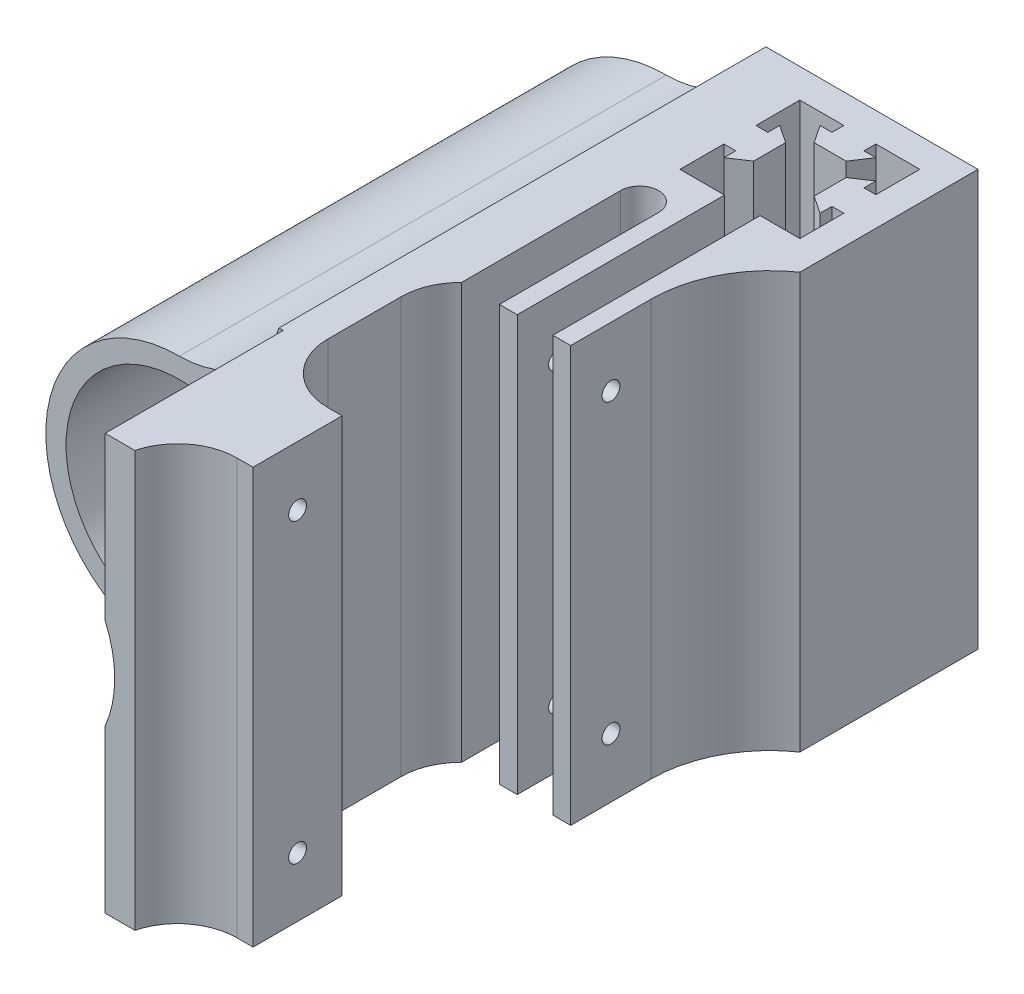
SolidWorks part; units mm, degrees
ref_plane "Front Plane" through (0, 0, 0) normal (0, 0, 1) x (1, 0, 0)
ref_plane "Top Plane" through (0, 0, 0) normal (0, 1, 0) x (1, 0, 0)
ref_plane "Right Plane" through (0, 0, 0) normal (1, 0, 0) x (0, 0, -1)
sketch "Sketch4" plane through (0, 0, 0) normal (0, 0, 1) x (1, 0, 0)
  line L0 (22.5, 0) -> (22.5, -60)
  line L21 (22.5, 0) -> (22.5, 60)
  line L22 (22.5, 60) -> (17.5, 60)
  line L23 (17.5, 60) -> (17.5, 40)
  line L24 (17.5, -60) -> (22.5, -60)
  line L25 (17.5, -40) -> (17.5, -60)
  circle A0 centre (0, 0) radius 19.1
  arc A1 (0, 22.5) -> (0, -22.5) centre (0, 0) ccw
  arc A2 (0, 22.5) -> (17.5, 40) centre (0, 40) ccw
  arc A3 (17.5, -40) -> (0, -22.5) centre (0, -40) ccw
  dimension "D1" = 38.2
  dimension "D2" = 45
  dimension "D3" = 60
  dimension "D8" = 17.5
  dimension "D9" = 17.5
  dimension "D6" = 40
  dimension "D7" = 40
  dimension "D4" = 60
  dimension "D5" = 5
extrude "Boss-Extrude4" add sketch "Sketch4" along normal blind 80
sketch "Sketch5" plane through (0, 0, 0) normal (0, 0, -1) x (-1, 0, 0)
  line L0 (-17.5, 60) -> (-22.5, 60)
  line L1 (-22.5, 60) -> (-22.5, -60)
  line L2 (-22.5, -60) -> (-17.5, -60)
  line L3 (-17.5, -60) -> (-17.5, -40)
  line L4 (-17.5, 60) -> (-17.5, 40)
  arc A0 (0, -22.5) -> (0, 22.5) centre (0, 0) ccw
  arc A1 (-17.5, 40) -> (0, 22.5) centre (0, 40) ccw
  arc A2 (0, -22.5) -> (-17.5, -40) centre (0, -40) ccw
  circle A3 centre (0, 0) radius 5
  dimension "D1" = 10
  dimension "D2" = 22.5
extrude "Boss-Extrude5" add sketch "Sketch5" along normal blind 2 contours A0 A1 L4 L0 L1 L2 L3 A2
sketch "Sketch6" plane through (0, 0, -2) normal (0, 0, -1) x (-1, 0, 0)
  circle A0 centre (0, 0) radius 5
  dimension "D1" = 10
extrude "Cut-Extrude1" cut sketch "Sketch6" against normal blind 2
sketch "Sketch7" plane through (0, 0, 80) normal (0, 0, 1) x (1, 0, 0)
  line L0 (17.5, 60) -> (17.5, 7.6525)
  line L1 (17.5, -60) -> (17.5, -7.6525)
  line L2 (17.5, -60) -> (22.5, -60)
  line L3 (22.5, -60) -> (22.5, 60)
  line L4 (22.5, 60) -> (17.5, 60)
  circle A0 centre (0, 0) radius 19.1 construction
  circle A1 centre (0, 0) radius 19.1 construction
  arc A2 (17.5, -7.6525) -> (17.5, 7.6525) centre (0, 0) ccw
extrude "Boss-Extrude7" add sketch "Sketch7" along normal blind 30 contours A2 L0 L4 L3 L2 L1
sketch "Sketch8" plane through (0, 0, -2) normal (0, 0, -1) x (-1, 0, 0)
  circle A0 centre (0, 0) radius 11
  dimension "D1" = 22
extrude "Cut-Extrude2" cut sketch "Sketch8" against normal blind 30
sketch "Sketch9" plane through (0, 0, -2) normal (0, 0, -1) x (-1, 0, 0)
  line L0 (0, 0) -> (13.5, 0)
  line L1 (0, 0) -> (-13.5, 0)
  line L2 (0, 0) -> (0, 13.5)
  line L3 (0, 0) -> (0, -13.5)
  circle A0 centre (0, 13.5) radius 1.5
  circle A1 centre (13.5, 0) radius 1.5
  circle A2 centre (0, -13.5) radius 1.5
  circle A3 centre (-13.5, 0) radius 1.5
  dimension "D5" = 3
  dimension "D6" = 3
  dimension "D7" = 3
  dimension "D8" = 3
  dimension "D1" = 13.5
  dimension "D2" = 13.5
  dimension "D3" = 13.5
  dimension "D4" = 13.5
extrude "Cut-Extrude3" cut sketch "Sketch9" against normal blind 30 contours A0 | A1 | A2 | A3
sketch "Sketch11" plane through (0, -60, 0) normal (0, -1, 0) x (1, 0, 0)
  line L1 (17.5, 110) -> (22.5, 110)
  line L2 (17.5, 110) -> (17.5, -2)
  line L3 (17.5, -2) -> (22.5, -2)
  line L4 (22.5, 110) -> (22.5, -2)
extrude "Boss-Extrude8" add sketch "Sketch11" along normal blind 20
sketch "Sketch12" plane through (0, 60, 0) normal (0, 1, 0) x (1, 0, 0)
  line L1 (17.5, 2) -> (22.5, 2)
  line L2 (17.5, 2) -> (17.5, -110)
  line L3 (17.5, -110) -> (22.5, -110)
  line L4 (22.5, 2) -> (22.5, -110)
extrude "Boss-Extrude9" add sketch "Sketch12" along normal blind 20
sketch "Sketch13" plane through (17.5, 0, 0) normal (-1, 0, 0) x (0, 0, 1)
  line L0 (-2, 60) -> (26, 60)
  line L1 (-2, 80) -> (-2, 40) construction
  line L2 (26, 60) -> (54, 60)
  line L3 (54, 60) -> (82, 60)
  line L4 (82, 60) -> (110, 60)
  line L5 (110, 80) -> (110, 7.6525) construction
  line L6 (-2, -60) -> (26, -60)
  line L7 (-2, -80) -> (-2, -40) construction
  line L8 (26, -60) -> (54, -60)
  line L9 (54, -60) -> (82, -60)
  line L10 (82, -60) -> (110, -60)
  line L11 (110, -80) -> (110, -7.6525) construction
  circle A0 centre (26, 60) radius 1.5
  circle A1 centre (54, 60) radius 1.5
  circle A2 centre (82, 60) radius 1.5
  circle A3 centre (82, -60) radius 1.5
  circle A4 centre (54, -60) radius 1.5
  circle A5 centre (26, -60) radius 1.5
  dimension "D7" = 3
  dimension "D8" = 3
  dimension "D9" = 3
  dimension "D10" = 3
  dimension "D11" = 3
  dimension "D12" = 3
  dimension "D1" = 28
  dimension "D2" = 28
  dimension "D3" = 28
  dimension "D4" = 28
  dimension "D5" = 28
  dimension "D6" = 28
extrude "Cut-Extrude4" cut sketch "Sketch13" against normal blind 20 contours A0 | A1 | A2 | A3 | A4 | A5
sketch "Sketch14" plane through (17.5, 0, 0) normal (-1, 0, 0) x (0, 0, 1)
  line L0 (95, 7.6525) -> (95, 37.6525)
  line L1 (110, 7.6525) -> (80, 7.6525) construction
  line L2 (95, -7.6525) -> (95, -37.6525)
  line L3 (110, -7.6525) -> (80, -7.6525) construction
  circle A0 centre (95, 37.6525) radius 1.5
  circle A1 centre (95, -37.6525) radius 1.5
  dimension "D3" = 3
  dimension "D4" = 3
  dimension "D1" = 30
  dimension "D2" = 30
extrude "Cut-Extrude5" cut sketch "Sketch14" against normal blind 20 contours A0 | A1
sketch "Sketch16" plane through (22.5, 0, 0) normal (1, 0, 0) x (0, 0, -1)
  line L0 (2, 80) -> (2, -80) construction
  line L1 (2, 35) -> (-28, 35)
  line L2 (2, 35) -> (2, -35)
  line L3 (2, -35) -> (-28, -35)
  line L4 (-28, 35) -> (-28, -35)
  dimension "D1" = 30
  dimension "D2" = 70
  dimension "D3" = 35
extrude "Boss-Extrude10" add sketch "Sketch16" along normal blind 30
sketch "Sketch21" plane through (0, 35, 0) normal (0, 1, 0) x (1, 0, 0)
  line L0 (27.4, -2.9) -> (47.6, -2.9)
  line L1 (27.4, -2.9) -> (27.4, -23.1)
  line L2 (27.4, -23.1) -> (47.6, -23.1)
  line L3 (47.6, -2.9) -> (47.6, -23.1)
  line L4 (34.8, -2.9) -> (34.8, -4.9)
  line L5 (34.8, -4.9) -> (32.8, -4.9)
  line L6 (32.8, -4.9) -> (34.8, -7.9)
  line L7 (34.8, -7.9) -> (40.2, -7.9)
  line L8 (37.5, -2.9) -> (37.5, -23.1) construction
  line L9 (27.4, -13) -> (47.6, -13) construction
  line L10 (40.2, -2.9) -> (40.2, -4.9)
  line L11 (40.2, -4.9) -> (42.2, -4.9)
  line L12 (42.2, -4.9) -> (40.2, -7.9)
  line L13 (29.4, -15.7) -> (29.4, -17.7)
  line L14 (27.4, -15.7) -> (29.4, -15.7)
  line L15 (29.4, -17.7) -> (32.4, -15.7)
  line L16 (32.4, -10.3) -> (32.4, -15.7)
  line L17 (29.4, -8.3) -> (32.4, -10.3)
  line L18 (29.4, -10.3) -> (29.4, -8.3)
  line L19 (27.4, -10.3) -> (29.4, -10.3)
  line L20 (47.6, -10.3) -> (45.6, -10.3)
  line L21 (45.6, -10.3) -> (45.6, -8.3)
  line L22 (45.6, -8.3) -> (42.6, -10.3)
  line L23 (42.6, -10.3) -> (42.6, -15.7)
  line L24 (45.6, -17.7) -> (42.6, -15.7)
  line L25 (45.6, -15.7) -> (45.6, -17.7)
  line L26 (47.6, -15.7) -> (45.6, -15.7)
  line L29 (52.5, 2) -> (52.5, -28) construction
  line L30 (34.9, -23.1) -> (40.9, -23.1)
  line L31 (34.9, -23.1) -> (34.9, -28)
  line L32 (34.9, -28) -> (40.9, -28)
  line L33 (40.9, -23.1) -> (40.9, -28)
  line L35 (52.5, 2) -> (22.5, 2) construction
  point P18 (37.5, -7.9)
  point P31 (42.6, -13)
  line M11 (22.5, -28) -> (52.5, -28)
  dimension "D1" = 3
  dimension "D2" = 2
  dimension "D3" = 3
  dimension "D4" = 15
  dimension "D5" = 2
  dimension "D6" = 2
  dimension "D7" = 7.4
  dimension "D8" = 2
  dimension "D9" = 7.4
  dimension "D10" = 2
  dimension "D11" = 2
  dimension "D12" = 20.2
  dimension "D13" = 20.2
  dimension "D14" = 15
  dimension "D16" = 6
  dimension "D17" = 7.5
  dimension "D18" = 15
extrude "Cut-Extrude6" cut sketch "Sketch21" against normal blind 70 contours L3 L26 L25 L24 L23 L22 L21 L20 L0 L10 L11 L12 L7 L6 L5 L4 L1 L19 L18 L17 L16 L15 L13 L14 L2 | L33 L2 L31 M11 region at (37.5, 35, 13.8018) region at (37.9, 35, 25.55)
sketch "Sketch23" plane through (0, 0, 28) normal (0, 0, 1) x (1, 0, 0)
  line L0 (52.5, -35) -> (40.9, -35) construction
  line L5 (40.9, 35) -> (43.9, 35)
  line L6 (40.9, 35) -> (40.9, -35)
  line L7 (40.9, -35) -> (43.9, -35)
  line L8 (43.9, 35) -> (43.9, -35)
  line L9 (34.9, -35) -> (22.5, -35) construction
  line L10 (22.5, 35) -> (25.5, 35)
  line L11 (22.5, 35) -> (22.5, -35)
  line L12 (22.5, -35) -> (25.5, -35)
  line L13 (25.5, 35) -> (25.5, -35)
  line L15 (34.9, 35) -> (31.9, 35)
  line L16 (34.9, 35) -> (34.9, -35)
  line L17 (34.9, -35) -> (31.9, -35)
  line L18 (31.9, 35) -> (31.9, -35)
  dimension "D1" = 3
  dimension "D2" = 3
  dimension "D3" = 3
extrude "Boss-Extrude11" add sketch "Sketch23" along normal blind 30
fillet "Fillet5" 2 edges at (25.5, 0, 28) (31.9, 0, 28) type full round first side face at (25.5, 0, 43) second side face at (31.9, 0, 43) middle face at (28.7, 0, 28)
fillet "Fillet6" radius 20 1 edges at (43.9, 0, 28)
sketch "Sketch26" plane through (17.5, 0, 0) normal (-1, 0, 0) x (0, 0, 1)
  line L1 (-2, -40) -> (110, -40)
  line L2 (-2, -40) -> (-2, -80)
  line L3 (-2, -80) -> (110, -80)
  line L4 (110, -40) -> (110, -80)
  line L5 (-2, 40) -> (110, 40)
  line L6 (-2, 40) -> (-2, 80)
  line L7 (-2, 80) -> (110, 80)
  line L8 (110, 40) -> (110, 80)
extrude "Cut-Extrude10" cut sketch "Sketch26" against normal blind 15
sketch "Sketch27" plane through (0, 0, -2) normal (0, 0, -1) x (-1, 0, 0)
  line L1 (-22.5, 35) -> (-15.6348, 35)
  line L2 (-22.5, 35) -> (-22.5, 41.8509)
  line L3 (-22.5, 41.8509) -> (-15.6348, 41.8509)
  line L4 (-15.6348, 35) -> (-15.6348, 41.8509)
  line L5 (-22.5, -35) -> (-14.5768, -35)
  line L6 (-22.5, -35) -> (-22.5, -40.8848)
  line L7 (-22.5, -40.8848) -> (-14.5768, -40.8848)
  line L8 (-14.5768, -35) -> (-14.5768, -40.8848)
  dimension "D1" = 6.8509
  dimension "D2" = 6.8652
  dimension "D3" = 7.9232
  dimension "D4" = 5.8848
extrude "Cut-Extrude11" cut sketch "Sketch27" against normal through all
sketch "Sketch28" plane through (0, 35, 0) normal (0, 1, 0) x (1, 0, 0)
  line L0 (22.5, -110) -> (22.5, -58) construction
  line L1 (22.5, -102.5) -> (34.9, -102.5)
  line L2 (22.5, -102.5) -> (22.5, -87.5)
  line L3 (22.5, -87.5) -> (34.9, -87.5)
  line L4 (34.9, -102.5) -> (34.9, -87.5)
  line L5 (34.9, -23.1) -> (34.9, -58) construction
  line L6 (22.5, -110) -> (17.5, -110) construction
  dimension "D1" = 0
  dimension "D2" = 15
  dimension "D3" = 7.5
extrude "Boss-Extrude12" add sketch "Sketch28" against normal blind 70
fillet "Fillet7" radius 10 2 edges at (22.5, 0, 87.5) (22.5, 0, 102.5)
sketch "Sketch29" plane through (34.9, 0, 0) normal (1, 0, 0) x (0, 0, -1)
  line L0 (-95, 35) -> (-95, -35) construction
  line L1 (-102.5, 35) -> (-87.5, 35) construction
  line L2 (-102.5, -35) -> (-87.5, -35) construction
  circle A0 centre (-95, 25) radius 1.5
  circle A1 centre (-95, -25) radius 1.5
  dimension "D1" = 3
  dimension "D2" = 3
  dimension "D3" = 10
  dimension "D4" = 10
extrude "Cut-Extrude12" cut sketch "Sketch29" against normal through all
sketch "Sketch30" plane through (43.9, 0, 0) normal (1, 0, 0) x (0, 0, -1)
  line L0 (-51.2164, 35) -> (-51.2164, -35) construction
  line L1 (-58, 35) -> (-44.4329, 35) construction
  line L2 (-58, -35) -> (-44.4329, -35) construction
  circle A0 centre (-51.2164, 25) radius 1.5
  circle A1 centre (-51.2164, -25) radius 1.5
  dimension "D1" = 3
  dimension "D2" = 3
  dimension "D3" = 10
  dimension "D4" = 10
extrude "Cut-Extrude13" cut sketch "Sketch30" against normal blind 15
fillet "Fillet8" radius 10 1 edges at (22.5, 0, 58)
